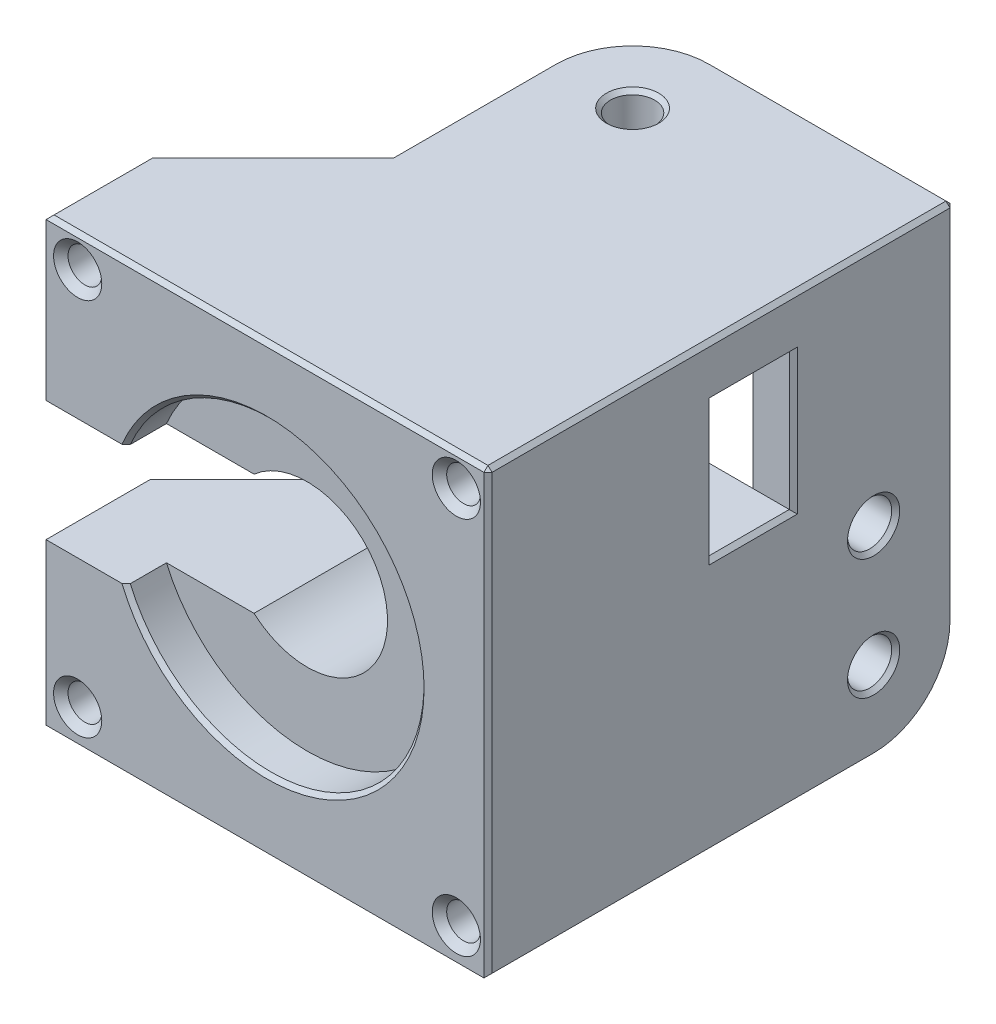
SolidWorks part; units mm, degrees
ref_plane "Front Plane" through (0, 0, 0) normal (0, 0, 1) x (1, 0, 0)
ref_plane "Top Plane" through (0, 0, 0) normal (0, 1, 0) x (1, 0, 0)
ref_plane "Right Plane" through (0, 0, 0) normal (1, 0, 0) x (0, 0, -1)
sketch "Sketch1" plane through (0, 0, 0) normal (0, 0, 1) x (1, 0, 0)
  line L1 (-27.5, 27.5) -> (27.5, 27.5)
  line L2 (-27.5, 27.5) -> (-27.5, -27.5)
  line L3 (-27.5, -27.5) -> (27.5, -27.5)
  line L4 (27.5, 27.5) -> (27.5, -27.5)
  line L5 (-27.5, 27.5) -> (27.5, -27.5) construction
  line L6 (-27.5, -27.5) -> (27.5, 27.5) construction
  point P0 (0, 0)
  dimension "D1" = 55
extrude "Boss-Extrude1" add sketch "Sketch1" along normal blind 28
sketch "Sketch9" plane through (0, 0, 28) normal (0, 0, 1) x (1, 0, 0)
  circle A0 centre (0, 0) radius 19.05
  dimension "D1" = 38.1
extrude "Cut-Extrude1" cut sketch "Sketch9" against normal blind 5
chamfer "Chamfer1" distance 0.5 angle 45 1 edges at (19.05, 0, 28)
sketch "Sketch10" plane through (0, 0, 23) normal (0, 0, 1) x (1, 0, 0)
  circle A0 centre (0, 0) radius 10
  dimension "D1" = 20
extrude "Cut-Extrude2" cut sketch "Sketch10" against normal through all
sketch "Sketch11" plane through (-27.5, 0, 0) normal (-1, 0, 0) x (0, 0, 1)
  line L0 (0, 27.5) -> (0, -27.5) construction
  line L1 (28, 7.5) -> (0, 7.5)
  line L2 (28, 7.5) -> (28, -7.5)
  line L3 (28, -7.5) -> (0, -7.5)
  line L4 (0, 7.5) -> (0, -7.5)
  line L5 (28, 27.5) -> (28, -27.5) construction
  point P6 (0, 0)
  dimension "D3" = 15
extrude "Cut-Extrude3" cut sketch "Sketch11" against normal up to surface (20.8856 mm away) up to face at (10, 0, 0)
sketch "Sketch12" plane through (0, 0, 28) normal (0, 0, 1) x (1, 0, 0)
  line L1 (23.565, 23.565) -> (-23.565, 23.565)
  line L2 (23.565, 23.565) -> (23.565, -23.565)
  line L3 (23.565, -23.565) -> (-23.565, -23.565)
  line L4 (-23.565, 23.565) -> (-23.565, -23.565)
  line L5 (23.565, 23.565) -> (-23.565, -23.565) construction
  line L6 (23.565, -23.565) -> (-23.565, 23.565) construction
  point P0 (0, 0)
  dimension "D1" = 47.13
hole_wizard "M5x0.8 Tapped Hole1" positions "Sketch13" profile "Sketch15" tap size "M5x0.8" standard "ANSI Metric" end condition through all
sketch "Sketch13" plane through (0, 0, 28) normal (0, 0, 1) x (1, 0, 0)
  point P0 (23.565, 23.565)
  point P3 (23.565, -23.565)
  point P6 (-23.565, -23.565)
  point P9 (-23.565, 23.565)
sketch "Sketch15" plane through (23.565, 23.565, 28) normal (1, 0, 0) x (0, -1, 0)
  line L0 (0, 0) -> (0, 28)
  line L1 (0, 28) -> (2.1, 28)
  line L2 (2.1, 28) -> (2.1, 0.9)
  line L3 (2.1, 0.9) -> (3, 0)
  line L5 (3, 0) -> (0, 0)
  line L6 (-2.1, 0.9) -> (-3, 0) construction
  line L11 (0, -6.35) -> (0, 107.95) construction
  dimension "Thru Tap Drill Dia." = 4.2
  dimension "Thru Tap Drill Depth" = 28
  dimension "Near C'Sink Dia." = 6
  dimension "Near C'Sink Angle" = 90
cosmetic thread "Hole Thread1" parameters "D2"=5
cosmetic thread "Hole Thread2" parameters "D2"=5
cosmetic thread "Hole Thread3" parameters "D2"=5
cosmetic thread "Hole Thread4" parameters "D2"=5
chamfer "Chamfer3" distance 15 angle 45 2 edges at (-27.5, -17.5, 0) (-27.5, 17.5, 0)
sketch "Sketch19" plane through (0, 0, 0) normal (0, 0, -1) x (-1, 0, 0)
  line L0 (-22.5, -27.5) -> (-27.5, -27.5)
  line L1 (12.5, -27.5) -> (-27.5, -27.5) construction
  line L2 (-27.5, -27.5) -> (-27.5, 27.5)
  line L3 (-27.5, 27.5) -> (12.5, 27.5)
  line L4 (12.5, 27.5) -> (12.5, 22.5)
  line L5 (12.5, 7.5) -> (12.5, 27.5) construction
  line L6 (12.5, 22.5) -> (-22.5, 22.5)
  line L7 (-22.5, 22.5) -> (-22.5, -27.5)
  dimension "D1" = 5
extrude "Boss-Extrude3" add sketch "Sketch19" along normal blind 30
sketch "Sketch20" plane through (0, 0, 0) normal (0, 0, -1) x (-1, 0, 0)
  line L12 (-22.5, -25.3749) -> (-22.5, -27.5)
  line L13 (-22.5, -27.5) -> (12.5, -27.5)
  line L14 (12.5, -27.5) -> (12.5, -7.5)
  line L15 (12.5, -7.5) -> (6.6144, -7.5)
  line L24 (6.6144, 7.5) -> (12.5, 7.5)
  line L25 (12.5, 7.5) -> (12.5, 22.5)
  line L26 (12.5, 22.5) -> (-21.7551, 22.5)
  line L27 (-22.5, 21.7551) -> (-22.5, -21.7551)
  line L28 (-22.5, -25.3749) -> (-22.5, -27.5)
  line L29 (-22.5, -27.5) -> (12.5, -27.5)
  line L30 (12.5, -27.5) -> (12.5, -7.5)
  line L31 (12.5, -7.5) -> (6.6144, -7.5)
  line L32 (6.6144, 7.5) -> (12.5, 7.5)
  line L33 (12.5, 7.5) -> (12.5, 22.5)
  line L34 (12.5, 22.5) -> (-21.7551, 22.5)
  line L35 (-22.5, 21.7551) -> (-22.5, -21.7551)
  arc A4 (6.6144, 7.5) -> (6.6144, -7.5) centre (0, 0) ccw
  arc A5 (-22.5, 21.7551) -> (-21.7551, 22.5) centre (-23.565, 23.565) ccw
  arc A9 (-22.5, -25.3749) -> (-22.5, -21.7551) centre (-23.565, -23.565) ccw
  arc A10 (6.6144, 7.5) -> (6.6144, -7.5) centre (0, 0) ccw
  arc A11 (-22.5, 21.7551) -> (-21.7551, 22.5) centre (-23.565, 23.565) ccw
  arc A12 (-22.5, -25.3749) -> (-22.5, -21.7551) centre (-23.565, -23.565) ccw
  dimension "D1" = 0
extrude "Boss-Extrude4" add sketch "Sketch20" along normal blind 10
sketch "Sketch26" plane through (0, 0, -10) normal (0, 0, -1) x (-1, 0, 0)
  line L1 (-27.5, 21) -> (12.5, 21)
  line L2 (-27.5, 21) -> (-27.5, 4)
  line L3 (-27.5, 4) -> (12.5, 4)
  line L4 (12.5, 21) -> (12.5, 4)
  line L5 (12.5, 22.5) -> (-21.7551, 22.5) construction
  line L6 (12.5, 7.5) -> (12.5, 22.5) construction
  line L7 (-27.5, 27.5) -> (-27.5, -27.5) construction
  point P10 (12.5, 15)
  dimension "D1" = 1.5
  dimension "D2" = 17
extrude "Cut-Extrude5" cut sketch "Sketch26" against normal blind 10
fillet "Fillet2" radius 10 2 edges at (-12.5, 25, -30) (25, -27.5, -30)
hole_wizard "M5 Clearance Hole1" positions "Sketch22" profile "Sketch23" hole size "M5" standard "ANSI Metric" end condition through all
sketch "Sketch22" plane through (0, 27.5, 0) normal (0, 1, 0) x (1, 0, 0)
  arc A0 (-2.5, 30) -> (-12.5, 20) centre (-2.5, 20) ccw construction
  point P0 (-2.5, 20)
sketch "Sketch23" plane through (-2.5, 27.5, -20) normal (1, 0, 0) x (0, 0, 1)
  line L0 (0, 0) -> (0, 55)
  line L1 (0, 55) -> (2.75, 55)
  line L2 (2.75, 55) -> (2.75, 0)
  line L5 (2.75, 0) -> (0, 0)
  line L11 (0, -6.35) -> (0, 107.95) construction
  dimension "Thru Hole Dia." = 5.5
  dimension "Thru Hole Depth" = 55
hole_wizard "M5 Clearance Hole2" positions "Sketch24" profile "Sketch25" hole size "M5" standard "ANSI Metric" end condition through all
sketch "Sketch24" plane through (27.5, 0, 0) normal (1, 0, 0) x (0, 0, -1)
  arc A0 (20, -27.5) -> (30, -17.5) centre (20, -17.5) ccw construction
  point P0 (20, -17.5)
  point P7 (20, -2.5)
  dimension "D1" = 15
sketch "Sketch25" plane through (27.5, -17.5, -20) normal (0, 1, 0) x (0, 0, -1)
  line L0 (0, 0) -> (0, 55)
  line L1 (0, 55) -> (2.75, 55)
  line L2 (2.75, 55) -> (2.75, 0)
  line L5 (2.75, 0) -> (0, 0)
  line L11 (0, -6.35) -> (0, 107.95) construction
  dimension "Thru Hole Dia." = 5.5
  dimension "Thru Hole Depth" = 55
chamfer "Chamfer4" distance 0.5 angle 45 18 edges at (-2.5, 27.5, -17.25) (0, 27.5, 28) (-27.5, 27.5, 21.5) (-20, 27.5, 7.5) (-12.5, 27.5, -10) (-9.5711, 27.5, -27.0711) (12.5, 27.5, -30) (27.5, 0, 28) (27.5, 27.5, -1) (27.5, 5, -30) (27.5, -24.5711, -27.0711) (27.5, -27.5, 4) (27.5, -2.5, -22.75) (27.5, -17.5, -22.75) (27.5, 4, -5) (27.5, 12.5, -10) (27.5, 21, -5) (27.5, 12.5, 0)
